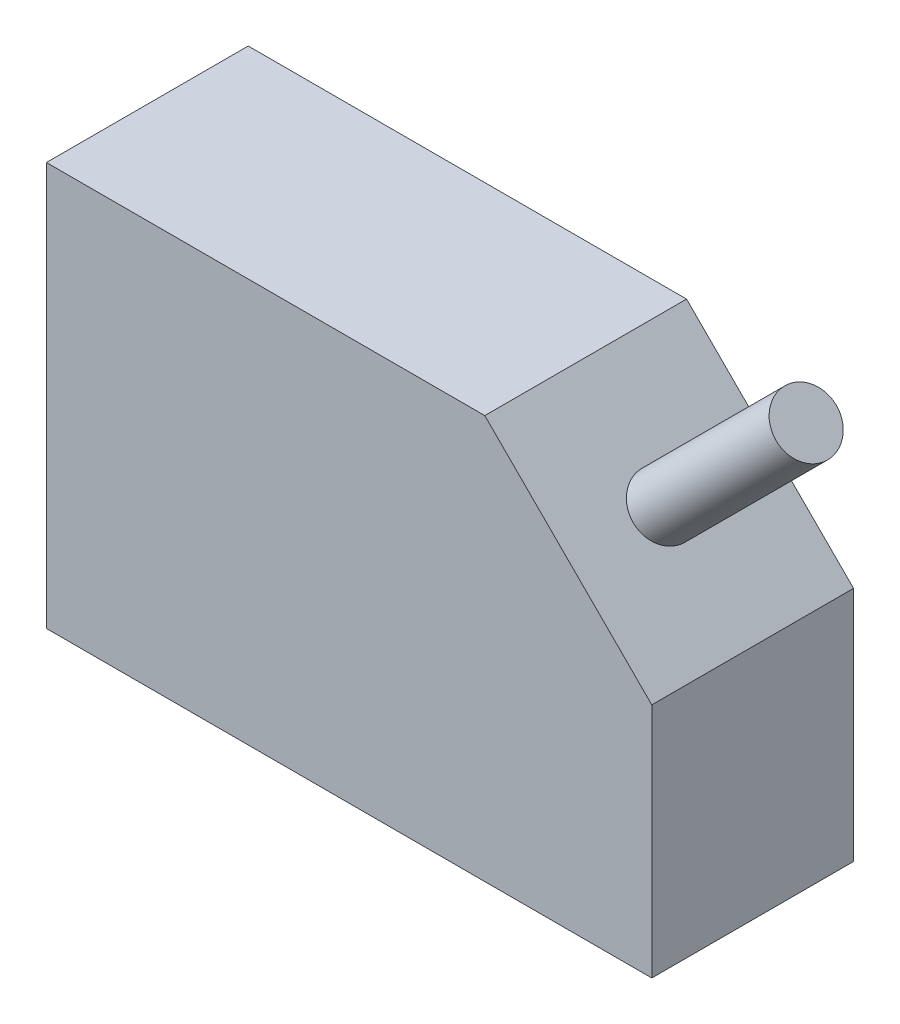
SolidWorks part; units mm, degrees
ref_plane "Front Plane" through (0, 0, 0) normal (0, 0, 1) x (1, 0, 0)
ref_plane "Top Plane" through (0, 0, 0) normal (0, 1, 0) x (1, 0, 0)
ref_plane "Right Plane" through (0, 0, 0) normal (1, 0, 0) x (0, 0, -1)
ref_plane "Plane1" through (0, 0, 0) normal (0, 0, -1) x (-1, 0, 0)
sketch "Sketch1" plane through (0, 0, 0) normal (0, 0, -1) x (-1, 0, 0)
  line L0 (-15, 1.724) -> (-15, -10)
  line L1 (-15, -10) -> (15, -10)
  line L2 (15, -10) -> (15, 10)
  line L3 (15, 10) -> (-6.724, 10)
  line L4 (-6.724, 10) -> (-15, 1.724)
extrude "Boss-Extrude1" add sketch "Sketch1" against normal blind 10
ref_plane "Plane2" through (0, 0, 5.2823) normal (0, 0, 1) x (1, 0, 0)
sketch "Sketch2" plane through (0, 0, 5.2823) normal (0, 0, 1) x (1, 0, 0)
  line L0 (18.9937, 11.8724) -> (17.9331, 12.9331)
  line L1 (17.9331, 12.9331) -> (10.862, 5.862)
  line L2 (10.862, 5.862) -> (11.9227, 4.8014)
  line L3 (11.9227, 4.8014) -> (18.9937, 11.8724)
  line L4 (18.4634, 13.4634) -> (10.3317, 5.3317) construction
revolve "Revolve1" add sketch "Sketch2" angle 360 about L4 reverse direction yes
